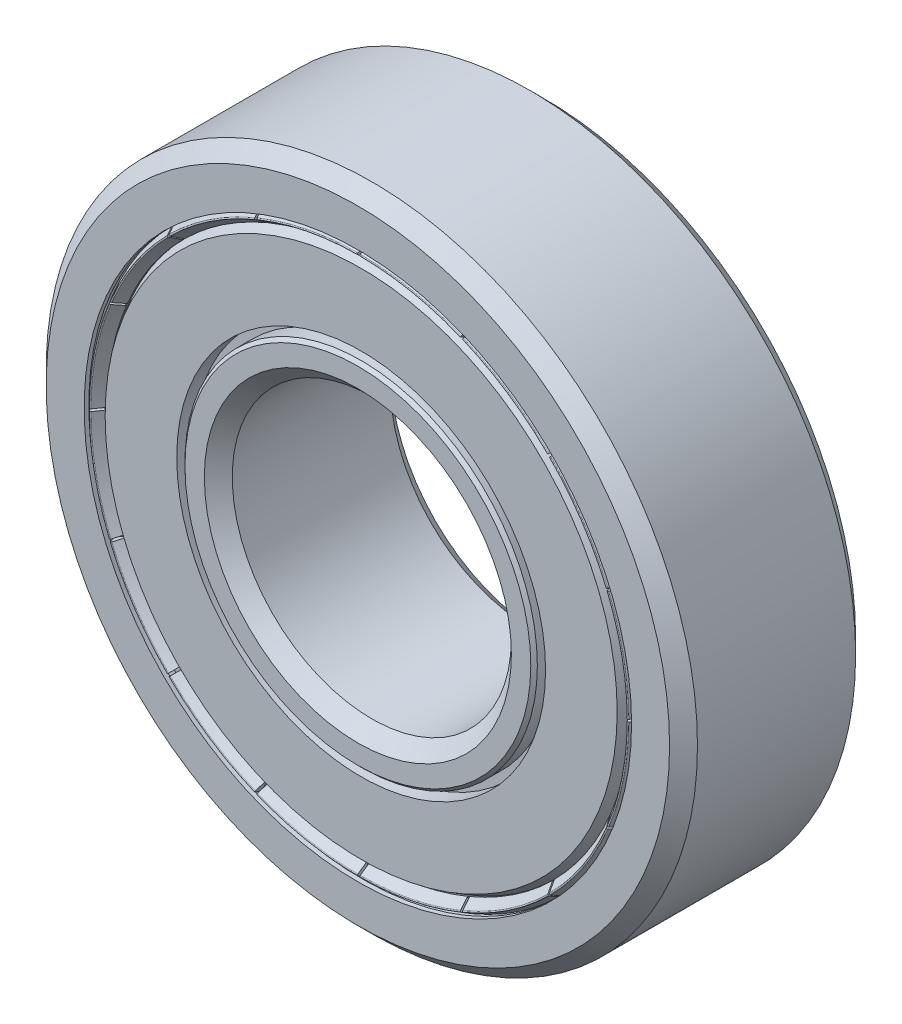
SolidWorks part; units mm, degrees
material "AISI 316 Stainless Steel Sheet (SS)"
ref_plane "Front Plane" through (0, 0, 0) normal (0, 0, 1) x (1, 0, 0)
ref_plane "Top Plane" through (0, 0, 0) normal (0, 1, 0) x (1, 0, 0)
ref_plane "Right Plane" through (0, 0, 0) normal (1, 0, 0) x (0, 0, -1)
sketch "Sketch1" plane through (0, 0, 0) normal (0, 0, 1) x (1, 0, 0)
  circle A0 centre (0, 0) radius 6
  circle A1 centre (0, 0) radius 14
  dimension "OD" = 28
  dimension "ID" = 12
sketch "Sketch2" plane through (0, 0, 0) normal (1, 0, 0) x (0, 0, -1)
  line L0 (-4, 14) -> (4, 14)
  line L1 (-4, 6) -> (-4, -6) construction
  line L2 (4, 14) -> (4, -14) construction
  line L3 (-4, 0) -> (4, 0) construction
  line L6 (0, 14) -> (0, 6) construction
  circle A0 centre (0, 10) radius 2.8 construction
  point P8 (0, 14)
  dimension "Approx. Ball Dia." = 5.6
  dimension "Width" = 8
  dimension "For Shaft Diameter" = 12
  dimension "For Housing ID" = 28
sketch "Sketch3" plane through (0, 0, 0) normal (1, 0, 0) x (0, 0, -1)
  line L0 (0, 0) -> (0, 12) construction
  line L1 (-4, 6) -> (-4, -6) construction
  line L2 (3.4, 14) -> (-3.4, 14)
  line L3 (-3.4, 14) -> (-4, 13.4)
  line L4 (-4, 13.4) -> (-4, 11.7669)
  line L5 (-4, 11.7669) -> (-3.8, 11.7669)
  line L6 (-3.8, 11.7669) -> (-3.8, 12.2834)
  line L7 (-3.8, 12.2834) -> (-3.6586, 12.4249)
  line L8 (-3.6586, 12.4249) -> (-1.4, 12.4249)
  line L10 (-4, 14) -> (4, 14) construction
  line L12 (-3.8, 12.2834) -> (-3.8, 12.8) construction
  line L13 (3.6586, 12.4249) -> (1.4, 12.4249)
  line L14 (3.8, 12.2834) -> (3.6586, 12.4249)
  line L15 (3.8, 11.7669) -> (3.8, 12.2834)
  line L16 (4, 11.7669) -> (3.8, 11.7669)
  line L17 (4, 13.4) -> (4, 11.7669)
  line L18 (3.4, 14) -> (4, 13.4)
  line L19 (3.4, 6) -> (-3.4, 6)
  line L20 (-3.4, 6) -> (-4, 6.6)
  line L21 (-4, 6.6) -> (-4, 7.4337)
  line L22 (-4, 7.4337) -> (-3.8586, 7.5751)
  line L23 (-3.8586, 7.5751) -> (-1.4, 7.5751)
  line L25 (3.8586, 7.5751) -> (1.4, 7.5751)
  line L26 (4, 7.4337) -> (3.8586, 7.5751)
  line L27 (4, 6.6) -> (4, 7.4337)
  line L28 (3.4, 6) -> (4, 6.6)
  circle A2 centre (0, 10) radius 2.8 construction
  arc A3 (-1.4, 12.4249) -> (1.4, 12.4249) centre (0, 10) cw
  arc A4 (-1.4, 7.5751) -> (1.4, 7.5751) centre (0, 10) ccw
  point P5 (0, 12.8)
  point P31 (0, 14)
  point P37 (0, 6)
  dimension "D1" = 45
  dimension "D2" = 0.2
  dimension "D3" = 2.8
  dimension "D4" = 0.6
revolve "Revolve1" add sketch "Sketch3" angle 360 about L3
sketch "Sketch4" plane through (0, 0, 0) normal (1, 0, 0) x (0, 0, -1)
  line L0 (0, 12.8) -> (0, 7.2)
  line L1 (0, 14) -> (0, 6) construction
  circle A0 centre (0, 10) radius 2.8 construction
  arc A1 (0, 7.2) -> (0, 12.8) centre (0, 10) cw
revolve "Revolve2" add sketch "Sketch4" angle 360 about L6
pattern_circular "CirPattern1" count 8 over 360 about axis through (0, 0, 4) along (0, 0, -1) of bodies 106
sketch "Sketch5" plane through (0, 0, 0) normal (1, 0, 0) x (0, 0, -1)
  line L0 (-2.8, 10) -> (-2.8, 7.5751) construction
  line L1 (-3.8586, 7.5751) -> (-1.4, 7.5751) construction
  line L3 (-2.8, 7.5751) -> (-3.1529, 7.5751)
  line L4 (-3.1529, 7.5751) -> (-3.1529, 7.928)
  line L5 (-3.1529, 7.928) -> (-3.8586, 7.928)
  line L6 (-3.8586, 7.928) -> (-3.8586, 11.0066)
  line L7 (-3.8586, 11.0066) -> (-3.1529, 11.414)
  line L8 (-3.1529, 11.414) -> (-2.8, 11.414)
  line L9 (-2.8, 11.414) -> (-2.8, 7.5751)
  line L10 (0, 10) -> (0, 14) construction
  line L11 (3.1529, 11.414) -> (2.8, 11.414)
  line L12 (3.8586, 11.0066) -> (3.1529, 11.414)
  line L13 (3.8586, 7.928) -> (3.8586, 11.0066)
  line L14 (3.1529, 7.928) -> (3.8586, 7.928)
  line L15 (3.1529, 7.5751) -> (3.1529, 7.928)
  line L16 (2.8, 7.5751) -> (3.1529, 7.5751)
  line L17 (2.8, 11.414) -> (2.8, 7.5751)
  line L18 (-3.8586, 11.0066) -> (-3.5057, 11.0066) construction
  line L19 (-3.5057, 11.0066) -> (-3.1529, 11.0066) construction
  line L20 (-3.1529, 11.0066) -> (-2.8, 11.0066) construction
  line L21 (-3.1529, 11.414) -> (-3.1529, 11.7669) construction
  circle A0 centre (0, 10) radius 2.8 construction
  dimension "D1" = 30
revolve "Revolve3" add sketch "Sketch5" angle 360 about L3
sketch "Sketch6" plane through (0, 0, 0) normal (1, 0, 0) x (0, 0, -1)
  line L0 (-3.4223, 11.7669) -> (-3.65, 11.7669)
  line L1 (-3.65, 11.7669) -> (-4, 11.5648)
  line L2 (-4, 11.5648) -> (-3.5423, 11.2444)
  line L4 (-3.8586, 11.0066) -> (-3.1529, 11.414) construction
  line L5 (-3.4223, 11.2585) -> (-3.4223, 11.7669)
  line L6 (-4, 11.7669) -> (-3.8, 11.7669) construction
  line L7 (-3.5423, 11.2444) -> (-3.5023, 11.2444)
  line L8 (-3.5023, 11.2444) -> (-3.4223, 11.2585)
  line L9 (-4, 13.4) -> (-4, -13.4) construction
  line L11 (-3.5023, 11.2444) -> (-3.4623, 11.2444) construction
  line L12 (-3.4623, 11.2444) -> (-3.4223, 11.2444) construction
  point P27 (-3.5362, 11.7669)
  dimension "D1" = 30
  dimension "D3" = 10
  dimension "D2" = 35
  dimension "D4" = 0.04
  dimension "D5" = 0.35
revolve "Revolve4" add sketch "Sketch6" angle 360 about L3
fillet "Fillet1" radius 0.04 1 edges at (11.5648, 0, 4)
sketch "Sketch7" plane through (0, 0, 0) normal (0, 0, 1) x (1, 0, 0)
  line L0 (-0.05, 11.7669) -> (-0.05, 11.8669)
  line L1 (-0.05, 11.7669) -> (0.05, 11.7669) construction
  line L2 (-0.05, 11.7669) -> (-0.05, 11.2444)
  line L3 (-0.05, 11.2444) -> (0.05, 11.2444) construction
  line L4 (0.05, 11.7669) -> (0.05, 11.2444)
  line L5 (-0.05, 11.8669) -> (0.05, 11.8669)
  line L6 (0.05, 11.8669) -> (0.05, 11.7669)
  line L7 (-0.05, 11.2444) -> (-0.05, 11.1444)
  line L8 (-0.05, 11.1444) -> (0.05, 11.1444)
  line L9 (0.05, 11.1444) -> (0.05, 11.2444)
  dimension "D1" = 0.1
extrude "Cut-Extrude1" cut sketch "Sketch7" along normal through all from vertex starting at point (0, 11.7669, 3.5362)
pattern_circular "CirPattern2" count 16 over 360 about axis through (0, 0, 4) along (0, 0, -1) of "Cut-Extrude1"
mirror "Mirror1" about plane through (0, 0, 0) normal (0, 0, 1) of bodies 120
equation "\"Approx. Ball Dia.@Sketch2\"=( \"OD@Sketch1\" - \"ID@Sketch1\" )  * .5 * .7"
equation "\"D2@Sketch3\"=\"Width@Sketch2\"*.025"
equation "\"D3@Sketch3\"=\"Approx. Ball Dia.@Sketch2\"*.5"
equation "\"D4@Sketch3\"=\"Width@Sketch2\"*.075"
equation "\"Approx No of Balls\"= ( pi * \"OD@Sketch1\" ) * .5 / \"Approx. Ball Dia.@Sketch2\""
equation "\"D1@CirPattern1\"=\"Approx No of Balls\""
equation "\"D4@Sketch6\"=\"D2@Sketch3\"*.2"
equation "\"D1@CirPattern2\"=\"Approx No of Balls\"*2"
equation "\"D5@Sketch6\"=\"D2@Sketch3\"*1.75"
equation "\"D1@Fillet1\"=\"d4@sketch6\""
